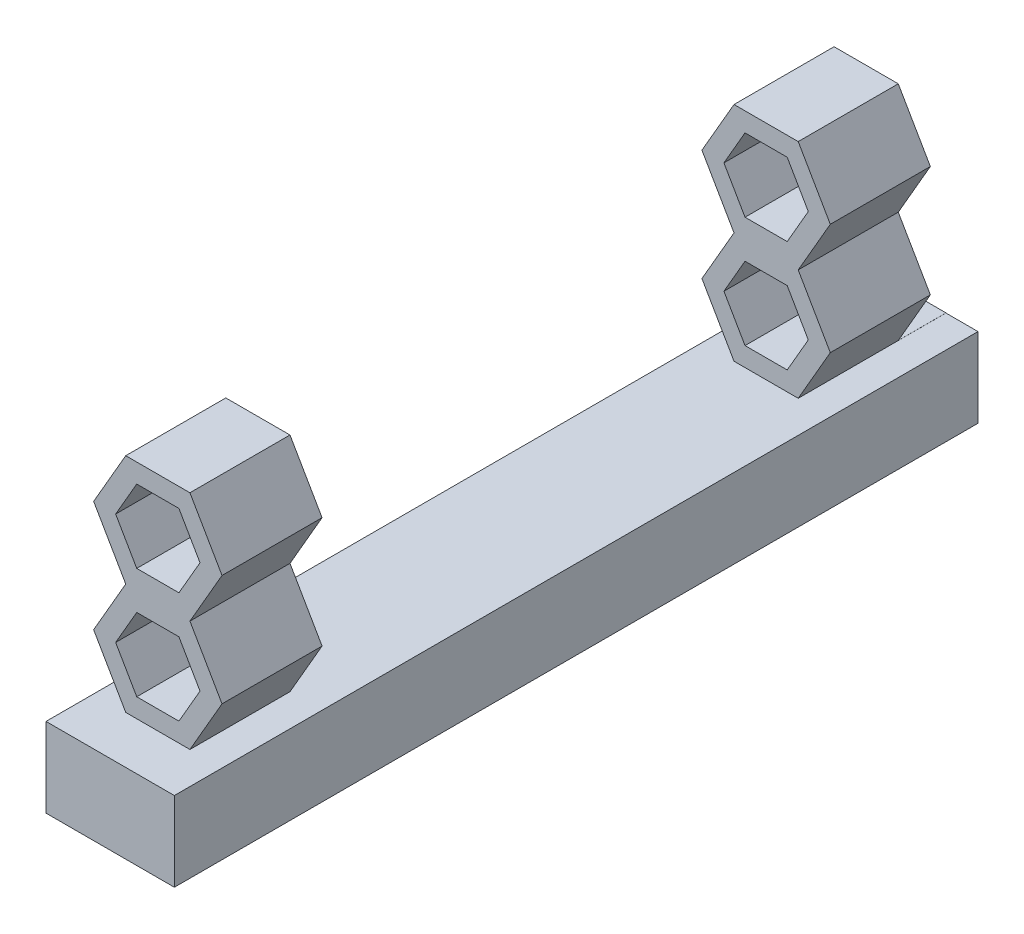
SolidWorks part; units mm, degrees
ref_plane "Front Plane" through (0, 0, 0) normal (0, 0, 1) x (1, 0, 0)
ref_plane "Top Plane" through (0, 0, 0) normal (0, 1, 0) x (1, 0, 0)
ref_plane "Right Plane" through (0, 0, 0) normal (1, 0, 0) x (0, 0, -1)
sketch "Sketch2" plane through (0, 0, 0) normal (0, 0, 1) x (1, 0, 0)
  line L0 (3.0311, 2.5013) -> (4.0415, 2.5013)
  line L1 (4.0415, 4.2513) -> (3.0311, 6.0013)
  line L2 (0, 0) -> (4.0415, 0)
  line L3 (0, 0) -> (0, 2.5013)
  line L4 (0, 2.5013) -> (1.0104, 2.5013)
  line L5 (4.0415, 0) -> (4.0415, 2.5013)
  line L7 (1.0104, 6.0013) -> (0, 4.2513)
  line L8 (0, 4.2513) -> (1.0104, 2.5013)
  line L10 (3.0311, 2.5013) -> (4.0415, 4.2513)
  line L11 (4.0415, 7.7513) -> (3.0311, 9.5013)
  line L12 (3.0311, 9.5013) -> (1.0104, 9.5013)
  line L13 (1.0104, 9.5013) -> (0, 7.7513)
  line L14 (0, 7.7513) -> (1.0104, 6.0013)
  line L16 (3.0311, 6.0013) -> (4.0415, 7.7513)
  line L17 (2.0207, 6.0013) -> (3.0311, 6.0013) [skipped]
  line L18 (3.0311, 6.0013) -> (2.0207, 6.0013) [skipped]
  line L19 (2.0207, 2.5013) -> (3.0311, 2.5013) [skipped]
  circle A0 centre (2.0207, 4.2513) radius 1.75 construction
  circle A1 centre (2.0207, 7.7513) radius 1.75 construction
  point P14 (2.0243, 4.2652)
  point P19 (2.4777, 2.5404)
  point P20 (2.4812, 2.5325)
  point P22 (1.9971, 4.2513)
  point P23 (2.0207, 7.7425)
  point P24 (2.0207, 4.2513)
  point P25 (2.3608, 2.5397)
extrude "Boss-Extrude1" add sketch "Sketch2" along normal blind 25.3 contours L1 L16 L11 L12 L13 L14 L7 L8 L4 L3 L2 L5 L0 L10
sketch "Sketch3" plane through (0, 0, 25.3) normal (0, 0, 1) x (1, 0, 0)
  line L0 (1.0104, 9.5013) -> (0, 7.7513) construction
  line L1 (3.3486, 7.7513) -> (2.6847, 8.9013)
  line L2 (2.6847, 8.9013) -> (1.3568, 8.9013)
  line L3 (1.3568, 8.9013) -> (0.6928, 7.7513)
  line L4 (0.6928, 7.7513) -> (1.3568, 6.6013)
  line L5 (1.3568, 6.6013) -> (2.6847, 6.6013)
  line L6 (2.6847, 6.6013) -> (3.3486, 7.7513)
  line L7 (3.0311, 6.0013) -> (4.0415, 7.7513) construction
  line L8 (4.0415, 7.7513) -> (3.0311, 9.5013) construction
  line L11 (3.3486, 4.2513) -> (2.6847, 5.4013)
  line L12 (2.6847, 5.4013) -> (1.3568, 5.4013)
  line L13 (1.3568, 5.4013) -> (0.6928, 4.2513)
  line L14 (0.6928, 4.2513) -> (1.3568, 3.1013)
  line L15 (1.3568, 3.1013) -> (2.6847, 3.1013)
  line L16 (2.6847, 3.1013) -> (3.3486, 4.2513)
  line L17 (1.0104, 6.0013) -> (0, 4.2513) construction
  line L18 (0, 4.2513) -> (1.0104, 2.5013) construction
  line L19 (4.0415, 4.2513) -> (3.0311, 6.0013) construction
  circle A0 centre (2.0207, 7.7513) radius 1.15 construction
  circle A1 centre (2.0207, 4.2513) radius 1.15 construction
  dimension "D1" = 0.6
  dimension "D2" = 0.6
  dimension "D3" = 0.6
  dimension "D4" = 0.6
  dimension "D5" = 0.6
  dimension "D6" = 0.6
extrude "Cut-Extrude1" cut sketch "Sketch3" against normal blind 25.3
sketch "Sketch14" plane through (0, 0, 0) normal (0, 0, -1) x (-1, 0, 0)
  line L1 (-4.2364, 9.6861) -> (0.2393, 9.6861)
  line L2 (-4.2364, 9.6861) -> (-4.2364, 2.5073)
  line L3 (-4.2364, 2.5073) -> (0.2393, 2.5073)
  line L4 (0.2393, 9.6861) -> (0.2393, 2.5073)
extrude "Cut-Extrude6" cut sketch "Sketch14" against normal blind 1.5
sketch "Sketch15" plane through (0, 0, 25.3) normal (0, 0, 1) x (1, 0, 0)
  line L1 (0, 9.6086) -> (4.0415, 9.6086)
  line L2 (0, 9.6086) -> (0, 2.5013)
  line L3 (0, 2.5013) -> (4.0415, 2.5013)
  line L4 (4.0415, 9.6086) -> (4.0415, 2.5013)
extrude "Cut-Extrude7" cut sketch "Sketch15" against normal blind 1.5
sketch "Sketch16" plane through (0, 9.5013, 0) normal (0, 1, 0) x (1, 0, 0)
  line L1 (-0.7522, -4.65) -> (4.5577, -4.65)
  line L2 (-0.7522, -4.65) -> (-0.7522, -20.65)
  line L3 (-0.7522, -20.65) -> (4.5577, -20.65)
  line L4 (4.5577, -4.65) -> (4.5577, -20.65)
  line L6 (1.0104, -1.5) -> (3.0311, -1.5) construction
  line L7 (3.0311, -23.8) -> (1.0104, -23.8) construction
  point P4 (1.9027, -4.65)
  dimension "D1" = 16
  dimension "D2" = 3.15
  dimension "D3" = 3.15
extrude "Cut-Extrude8" cut sketch "Sketch16" against normal blind 7
